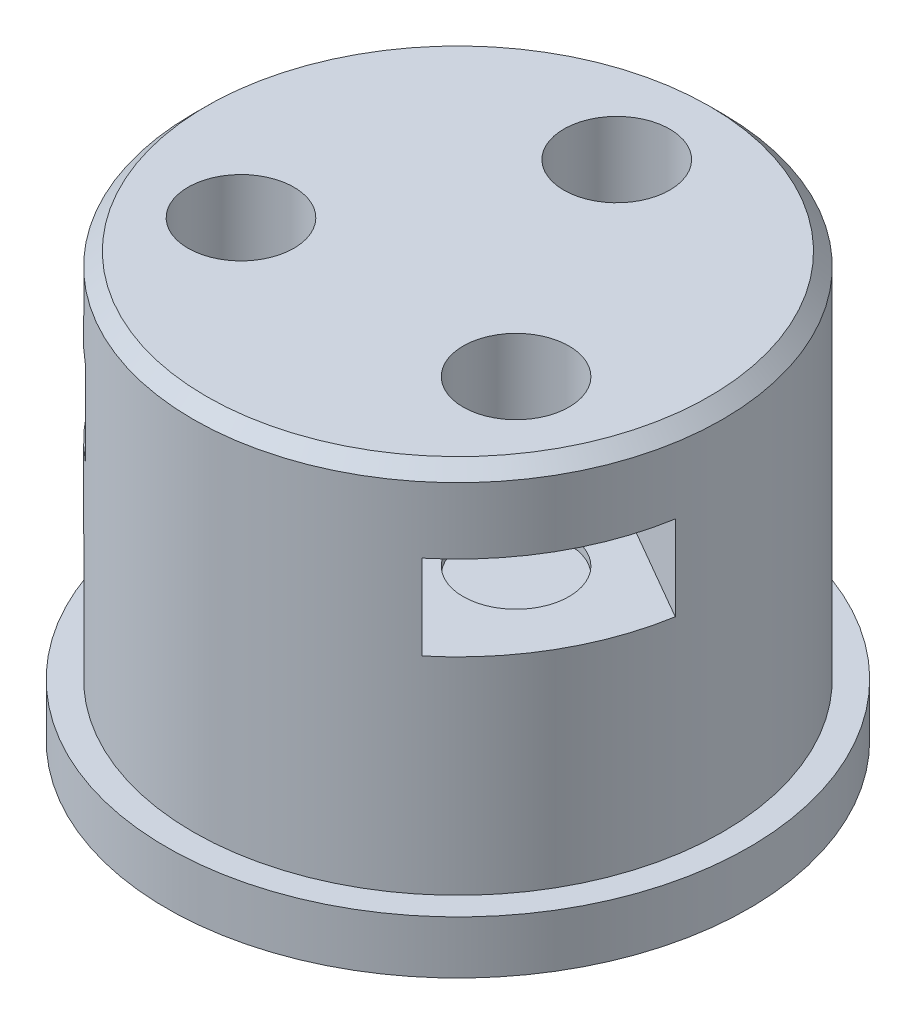
SolidWorks part; units mm, degrees
material "PLA"
ref_plane "Front Plane" through (0, 0, 0) normal (0, 0, 1) x (1, 0, 0)
ref_plane "Top Plane" through (0, 0, 0) normal (0, 1, 0) x (1, 0, 0)
ref_plane "Right Plane" through (0, 0, 0) normal (1, 0, 0) x (0, 0, -1)
sketch "Sketch1" plane through (0, 0, 0) normal (0, 1, 0) x (1, 0, 0)
  circle A0 centre (0, 0) radius 10
  circle A1 centre (0, 0) radius 8 construction
  dimension "D1" = 20
  dimension "D2" = 16
extrude "Boss-Extrude1" add sketch "Sketch1" along normal blind 16
sketch "Sketch2" plane through (0, 0, 0) normal (0, -1, 0) x (1, 0, 0)
  circle A0 centre (0, 0) radius 10 construction
  circle A1 centre (0, 0) radius 10
  circle A2 centre (0, 0) radius 11
extrude "Boss-Extrude2" add sketch "Sketch2" against normal blind 2
sketch "Sketch3" plane through (0, 0, 0) normal (0, -1, 0) x (1, 0, 0)
  circle A0 centre (0, 0) radius 8
  dimension "D1" = 16
extrude "Cut-Extrude1" cut sketch "Sketch3" against normal blind 6.5
sketch "Sketch4" plane through (0, 16, 0) normal (0, 1, 0) x (1, 0, 0)
  circle A0 centre (0, 0) radius 6 construction
  circle A1 centre (0, 6) radius 2
  circle A2 centre (5.1962, -3) radius 2
  circle A3 centre (-5.1962, -3) radius 2
  point P14 (0, 0)
  dimension "D1" = 12
  dimension "D2" = 4
  dimension "D3" = 3
extrude "Cut-Extrude2" cut sketch "Sketch4" against normal blind 6.5
sketch "Sketch5" plane through (0, 16, 0) normal (0, 1, 0) x (1, 0, 0)
  line L0 (-3.5, 8.0207) -> (-3.5, 9.3675)
  line L1 (0, 1.9585) -> (3.5, 3.9793)
  line L2 (3.5, 3.9793) -> (3.5, 8.0207)
  line L3 (3.5, 8.0207) -> (0, 10.0415)
  line L4 (0, 10.0415) -> (-3.5, 8.0207)
  line L5 (-3.5, 8.0207) -> (-3.5, 3.9793)
  line L6 (-3.5, 3.9793) -> (0, 1.9585)
  line L7 (3.5, 8.0207) -> (3.5, 9.3675)
  line L8 (8.6962, -0.9793) -> (9.8625, -1.6527)
  line L9 (8.6962, -0.9793) -> (5.1962, 1.0415)
  line L10 (8.6962, -5.0207) -> (8.6962, -0.9793)
  line L11 (5.1962, -7.0415) -> (8.6962, -5.0207)
  line L12 (5.1962, -7.0415) -> (6.3625, -7.7148)
  line L13 (1.6962, -5.0207) -> (5.1962, -7.0415)
  line L14 (1.6962, -0.9793) -> (1.6962, -5.0207)
  line L15 (5.1962, 1.0415) -> (1.6962, -0.9793)
  line L16 (-5.1962, -7.0415) -> (-6.3625, -7.7148)
  line L17 (-5.1962, -7.0415) -> (-1.6962, -5.0207)
  line L18 (-8.6962, -5.0207) -> (-5.1962, -7.0415)
  line L19 (-8.6962, -0.9793) -> (-8.6962, -5.0207)
  line L20 (-8.6962, -0.9793) -> (-9.8625, -1.6527)
  line L21 (-5.1962, 1.0415) -> (-8.6962, -0.9793)
  line L22 (-1.6962, -0.9793) -> (-5.1962, 1.0415)
  line L23 (-1.6962, -5.0207) -> (-1.6962, -0.9793)
  circle A0 centre (0, 6) radius 3.5 construction
  circle A1 centre (0, 0) radius 6 construction
  circle A3 centre (-5.1962, -3) radius 2
  circle A4 centre (-5.1962, -3) radius 2
  circle A5 centre (5.1962, -3) radius 2
  circle A6 centre (5.1962, -3) radius 2
  circle A7 centre (0, 6) radius 2
  circle A8 centre (0, 6) radius 2
  circle A9 centre (0, 0) radius 10 construction
  circle A10 centre (0, 0) radius 10
  point P50 (0, 0)
  circle M11 centre (0, 6) radius 2
  circle M12 centre (5.1962, -3) radius 2
  circle M13 centre (-5.1962, -3) radius 2
  circle M15 centre (0, 0) radius 10
  dimension "D5" = 7
  dimension "D4" = 0
  dimension "D6" = 3
extrude "Cut-Extrude3" cut sketch "Sketch5" against normal blind 3.2 from offset 3 contours L18 L16 M15 | L17 L23 L22 L21 L19 L18 M15 M13 | L19 L20 M15 | L5 L6 L1 L2 L3 L4 M15 M11 | L4 L0 M15 | L3 L7 M15 | L10 L8 M15 | L9 L15 L14 L13 L11 L10 M15 M12 | L11 L12 M15 region at (-2.2825, 16, -9.2115) region at (-1.7328, 16, -8.9179) region at (-9.1186, 16, 2.629) region at (2.2825, 16, -9.2115) region at (-6.8927, 16, 0.0615) region at (-6.8361, 16, 6.5825) region at (9.1186, 16, 2.629) region at (6.8361, 16, 6.5825) region at (8.5892, 16, 2.9583) offset against normal yes
sketch "Sketch6" plane through (0, 0, 0) normal (0, -1, 0) x (1, 0, 0)
  circle A0 centre (0, 0) radius 8
  circle A1 centre (0, 0) radius 7
  circle A2 centre (0, 0) radius 8 construction
extrude "Boss-Extrude3" add sketch "Sketch6" against normal up to surface (6.5 mm away) from offset 5 up to face at (0, 6.5, -8) offset against normal yes
chamfer "Chamfer1" distance 0.5 angle 45 1 edges at (0, 16, 10)
equation "\"Ns\" = 48"
equation "\"Np_b\" = 48"
equation "\"Np_s\" = 32"
equation "\"Nr_b\" = 144"
equation "\"module\" = 0.6"
equation "\"pressure_angle\" = 20.0"
equation "\"h_a\" = 0.6"
equation "\"h_f\" = 0.75"
equation "\"clr_tip_root\" = 0.15000000000000002"
equation "\"dp_r_b\" = 86.39999999999999"
equation "\"db_r_b\" = 81.18944243590248"
equation "\"fw_r_b\" = 34.81179682049524"
equation "\"alpha_r_b\" = 0.8539582918412414"
equation "\"beta_r_b\" = 2.957916583682483"
equation "\"bearing_ID\" = 65"
equation "\"bearing_OD\" = 85"
equation "\"bearing_height\" = 10"
equation "\"clearance_planet\" = 1.5"
equation "\"case_dist\" = 6.5"
equation "\"Motor_case_OD_max\" = 131.3"
equation "\"case_mounting_PCD\" = 123.8"
equation "\"bearing mount thickness\" = 8"
equation "\"case_mounting_hole_dia\" = 3"
equation "\"output_mounting_PCD\" = 93"
equation "\"output_mounting_hole_dia\" = 4"
equation "\"clearance_case_mount_holes_shell_thickness\" = 1"
equation "\"motor_case_OD_base\" = 121.8"
equation "\"sec_carrier_thickness\" = 5"
equation "\"sun_coupler_hub_thickness\" = 4"
equation "\"clearance_sun_coupler_sec_carrier\" = 1.5"
equation "\"clearance_motor_and_case\" = 5"
equation "\"motor_OD\" = 106.8"
equation "\"Motor_case_thickness\" = 2.5"
equation "\"Motor_case_ID\" = 116.8"
equation "\"case_mounting_hole_shift\" = 1.0"
equation "\"output_mounting_nut_wrench_size\" = 7"
equation "\"output_mounting_nut_thickness\" = 3.2"
equation "\"case_mounting_hole_allen_socket_dia\" = 5.5"
equation "\"output_mounting_nut_depth\" = 3"
equation "\"case_mounting_bolt_depth\" = 4.5"
equation "\"ring_radial_thickness\" = 5"
equation "\"ring_OD_b\" = 96.39999999999999"
equation "\"ring_to_chamfer_clearance\" = 1.5"
equation "\"Motor_case_OD_base_to_chamfer\" = 5"
equation "\"pattern_offset_from_motor_case_OD_base\" = 3"
equation "\"pattern_bulge_dia\" = 3"
equation "\"pattern_num_bulge\" = 18"
equation "\"pattern_depth\" = 2"
equation "\"motor_height\" = 47.6"
equation "\"case_mounting_wrench_size\" = 5.5"
equation "\"case_mounting_nut_clearance\" = 2"
equation "\"base_plate_thickness\" = 4"
equation "\"case_mounting_nut_thickness\" = 2.4"
equation "\"case_mounting_surface_height\" = 4"
equation "\"motor_mount_hole_PCD\" = 40"
equation "\"motor_mount_hole_dia\" = 5"
equation "\"motor_mount_hole_num\" = 4"
equation "\"central_hole_offset_from_motor_mount_PCD\" = 5"
equation "\"wire_slot_dist_from_center\" = 45.5"
equation "\"wire_slot_length\" = 10"
equation "\"wire_slot_radius\" = 3"
equation "\"driver_upper_holes_dist_from_center\" = 29"
equation "\"driver_lower_holes_dist_from_center\" = 13"
equation "\"driver_side_holes_dist_from_center\" = 22.5"
equation "\"driver_mount_holes_dia\" = 3"
equation "\"driver_mount_inserts_OD\" = 4.8"
equation "\"driver_mount_thickness\" = 1.5"
equation "\"driver_mount_height\" = 6"
equation "\"air_flow_hole_offset\" = 3"
equation "\"pressure angle\" = 20.0"
equation "\"h_b\" = 0.75"
equation "\"fw_p_s\" = 30.231545005724083"
equation "\"num_planet\" = 4"
equation "\"planet_pin_bolt_dia\" = 5"
equation "\"planet_pin_socket_head_dia\" = 8.5"
equation "\"carrier_PCD\" = 57.599999999999994"
equation "\"planet_shaft_dia\" = 8"
equation "\"planet_shaft_step_offset\" = 1"
equation "\"carrier_trapezoidal_support_sun_offset\" = 5"
equation "\"carrier_trapezoidal_support_hole_PCD_offset_bearing_ID\" = 4"
equation "\"carrier_trapezoidal_support_hole_dia\" = 3"
equation "\"carrier_trapezoidal_support_hole_socket_head_dia\" = 5.5"
equation "\"carrier_bearing_step_width\" = 1.5"
equation "\"standard_clearance_1_5mm\" = 1.5"
equation "\"standard_fillet_1_5mm\" = 1.5"
equation "\"sun_shaft_bearing_OD\" = 16"
equation "\"sun_shaft_bearing_width\" = 5"
equation "\"standard_bearing_insertion_chamfer\" = 0.5"
equation "\"carrier_trapezoidal_support_hole_wrench_size\" = 5.5"
equation "\"planet_pin_bolt_wrench_size\" = 8"
equation "\"planet_bearing_OD\" = 12"
equation "\"planet_bearing_width\" = 3.5"
equation "\"planet_bore\" = 10"
equation "\"motor_output_hole_PCD\" = 23"
equation "\"motor_output_hole_dia\" = 4"
equation "\"motor_output_hole_num\" = 4"
equation "\"dp_s\" = 28.799999999999997"
equation "\"db_s\" = 27.06314747863416"
equation "\"fw_s_calc\" = 7.664359769718526"
equation "\"alpha_s\" = 0.8539582918412343"
equation "\"beta_s\" = 2.0420834163175314"
equation "\"dp_p_b\" = 28.799999999999997"
equation "\"db_p_b\" = 27.06314747863416"
equation "\"alpha_p_b\" = 0.8539582918412343"
equation "\"beta_p_b\" = 2.0420834163175314"
equation "\"sun_shaft_bearing_ID\" = 8"
equation "\"sun_hub_dia\" = 30.0"
equation "\"sun_central_bolt_dia\" = 5"
equation "\"sun_central_bolt_socket_head_dia\" = 8.5"
equation "\"fw_s_used\" = 72.54334182621932"
equation "\"motor_output_hole_CSK_OD\" = 8"
equation "\"motor_output_hole_CSK_head_height\" = 2.0"
equation "\"bearing_retainer_thickness\" = 2"
equation "\"fw_p_b\" = 34.81179682049524"
equation "\"dp_p_s\" = 19.2"
equation "\"db_p_s\" = 18.04209831908944"
equation "\"alpha_p_s\" = 0.8539582918412556"
equation "\"beta_p_s\" = 3.917083416317489"
equation "\"Nr_s\" = 128"
equation "\"clr_tip_root_s\" = 0.15000000000000002"
equation "\"dp_r_s\" = 76.8"
equation "\"db_r_s\" = 72.16839327635776"
equation "\"fw_r_s\" = 28.731545005724083"
equation "\"alpha_r_s\" = 0.8539582918412556"
equation "\"beta_r_s\" = 3.114166583682511"
equation "\"D1@Boss-Extrude1\"=\"bearing_height\" + \"carrier_thickness\" + \"carrier_small_ring_inner_bearing_flap\""
equation "\"D1@Cut-Extrude1\"=\"sun_shaft_bearing_width\" + \"standard_clearance_1_5mm\""
equation "\"D5@Sketch5\"=\"small_ring_output_wall_to_bearing_shaft_attachement_nut_wrench\""
equation "\"small_ring_case_thickness\" = 4"
equation "\"carrier_thickness\" = 4"
equation "\"small_ring_output_wall_thickness\" = 5"
equation "\"small_ring_output_wall_to_bearing_shaft_attachement_hole_dia\" = 4"
equation "\"small_ring_output_wall_to_bearing_shaft_attachement_hole_pcd\" = 12"
equation "\"small_ring_output_wall_to_bearing_shaft_attachement_hole_num\" = 3"
equation "\"small_ring_output_wall_to_bearing_shaft_attachement_hole_CSK_OD\" = 8"
equation "\"small_ring_output_wall_to_bearing_shaft_attachement_hole_CSK_head_height\" = 2.0"
equation "\"carrier_small_ring_inner_bearing_ID\" = 20"
equation "\"carrier_small_ring_inner_bearing_OD\" = 32"
equation "\"carrier_small_ring_inner_bearing_height\" = 7"
equation "\"D1@Sketch1\"=\"carrier_small_ring_inner_bearing_ID\""
equation "\"D2@Sketch1\"=\"sun_shaft_bearing_OD\""
equation "\"D1@Sketch2\"=\"standard_clearance_1_5mm\"*2/3"
equation "\"D1@Sketch3\"=\"sun_shaft_bearing_OD\""
equation "\"D1@Sketch4\"=\"small_ring_output_wall_to_bearing_shaft_attachement_hole_pcd\""
equation "\"D2@Sketch4\"=\"small_ring_output_wall_to_bearing_shaft_attachement_hole_dia\""
equation "\"D3@Sketch4\"=\"small_ring_output_wall_to_bearing_shaft_attachement_hole_num\""
equation "\"D6@Sketch5\"=\"small_ring_output_wall_to_bearing_shaft_attachement_hole_num\""
equation "\"D19@Cut-Extrude3\"=\"standard_clearance_1_5mm\"*2"
equation "\"D1@Sketch6\"=\"standard_clearance_1_5mm\"*2/3"
equation "\"D19@Boss-Extrude3\"=\"sun_shaft_bearing_width\""
equation "\"small_ring_output_wall_to_bearing_shaft_attachement_hole_depth\" = 6.5"
equation "\"small_ring_output_wall_to_bearing_shaft_attachement_nut_wrench\" = 7"
equation "\"small_ring_output_wall_to_bearing_shaft_attachement_nut_thickness\" = 3.2"
equation "\"carrier_small_ring_inner_bearing_flap\" = 2"
equation "\"D1@Boss-Extrude2\"=\"carrier_small_ring_inner_bearing_flap\""
equation "\"D1@Cut-Extrude2\"=\"small_ring_output_wall_to_bearing_shaft_attachement_hole_depth\""
equation "\"D1@Cut-Extrude3\"=\"small_ring_output_wall_to_bearing_shaft_attachement_nut_thickness\""
equation "\"D1@Chamfer1\"=\"standard_bearing_insertion_chamfer\""
